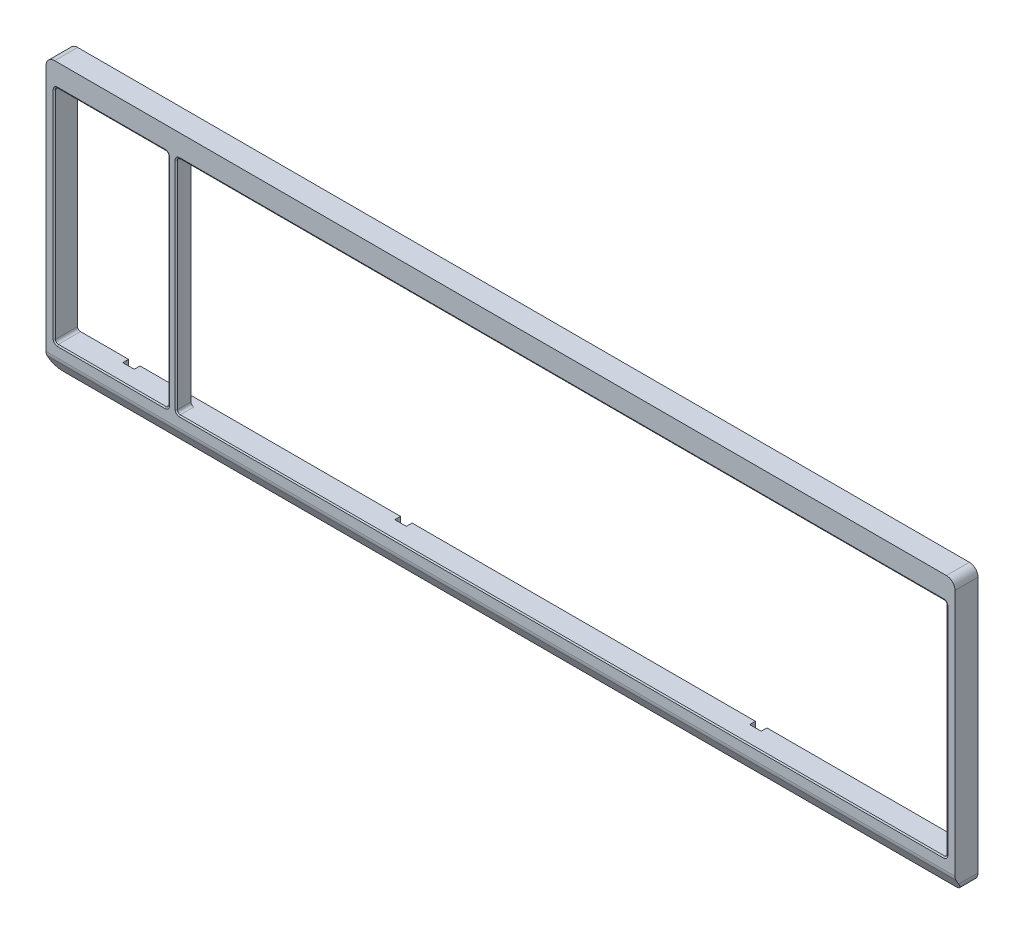
SolidWorks part; units mm, degrees
note: The reader was unsure of these and kept them because the rebuilt part matched: shared geometry of "Sketch3<3>", "Sketch8<3>", "Sketch11<3>".
ref_plane "Front Plane" through (0, 0, 0) normal (0, 0, 1) x (1, 0, 0)
ref_plane "Top Plane" through (0, 0, 0) normal (0, 1, 0) x (1, 0, 0)
ref_plane "Right Plane" through (0, 0, 0) normal (1, 0, 0) x (0, 0, -1)
sketch "Model" plane through (0, 0, 0) normal (0, 0, 1) x (1, 0, 0)
  line L0 (3.025, -2.525) -> (16.025, -2.525)
  line L1 (3.025, -16.525) -> (16.025, -16.525)
  line L2 (2.525, -3.025) -> (2.525, -16.025)
  line L3 (16.525, -3.025) -> (16.525, -16.025)
  line L4 (22.075, -2.525) -> (35.075, -2.525)
  line L5 (22.075, -16.525) -> (35.075, -16.525)
  line L6 (21.575, -3.025) -> (21.575, -16.025)
  line L7 (35.575, -3.025) -> (35.575, -16.025)
  line L8 (45.8875, -2.525) -> (58.8875, -2.525)
  line L9 (45.8875, -16.525) -> (58.8875, -16.525)
  line L10 (45.3875, -3.025) -> (45.3875, -16.025)
  line L11 (59.3875, -3.025) -> (59.3875, -16.025)
  line L12 (64.9375, -2.525) -> (77.9375, -2.525)
  line L13 (64.9375, -16.525) -> (77.9375, -16.525)
  line L14 (64.4375, -3.025) -> (64.4375, -16.025)
  line L15 (78.4375, -3.025) -> (78.4375, -16.025)
  line L16 (83.9875, -2.525) -> (96.9875, -2.525)
  line L17 (83.9875, -16.525) -> (96.9875, -16.525)
  line L18 (83.4875, -3.025) -> (83.4875, -16.025)
  line L19 (97.4875, -3.025) -> (97.4875, -16.025)
  line L20 (103.0375, -2.525) -> (116.0375, -2.525)
  line L21 (103.0375, -16.525) -> (116.0375, -16.525)
  line L22 (102.5375, -3.025) -> (102.5375, -16.025)
  line L23 (116.5375, -3.025) -> (116.5375, -16.025)
  line L24 (122.0875, -2.525) -> (135.0875, -2.525)
  line L25 (122.0875, -16.525) -> (135.0875, -16.525)
  line L26 (121.5875, -3.025) -> (121.5875, -16.025)
  line L27 (135.5875, -3.025) -> (135.5875, -16.025)
  line L28 (141.1375, -2.525) -> (154.1375, -2.525)
  line L29 (141.1375, -16.525) -> (154.1375, -16.525)
  line L30 (140.6375, -3.025) -> (140.6375, -16.025)
  line L31 (154.6375, -3.025) -> (154.6375, -16.025)
  line L32 (160.1875, -2.525) -> (173.1875, -2.525)
  line L33 (160.1875, -16.525) -> (173.1875, -16.525)
  line L34 (159.6875, -3.025) -> (159.6875, -16.025)
  line L35 (173.6875, -3.025) -> (173.6875, -16.025)
  line L36 (179.2375, -2.525) -> (192.2375, -2.525)
  line L37 (179.2375, -16.525) -> (192.2375, -16.525)
  line L38 (178.7375, -3.025) -> (178.7375, -16.025)
  line L39 (192.7375, -3.025) -> (192.7375, -16.025)
  line L40 (198.2875, -2.525) -> (211.2875, -2.525)
  line L41 (198.2875, -16.525) -> (211.2875, -16.525)
  line L42 (197.7875, -3.025) -> (197.7875, -16.025)
  line L43 (211.7875, -3.025) -> (211.7875, -16.025)
  line L44 (217.3375, -2.525) -> (230.3375, -2.525)
  line L45 (217.3375, -16.525) -> (230.3375, -16.525)
  line L46 (216.8375, -3.025) -> (216.8375, -16.025)
  line L47 (230.8375, -3.025) -> (230.8375, -16.025)
  line L48 (236.3875, -2.525) -> (249.3875, -2.525)
  line L49 (236.3875, -16.525) -> (249.3875, -16.525)
  line L50 (235.8875, -3.025) -> (235.8875, -16.025)
  line L51 (249.8875, -3.025) -> (249.8875, -16.025)
  line L52 (255.4375, -2.525) -> (268.4375, -2.525)
  line L53 (255.4375, -16.525) -> (268.4375, -16.525)
  line L54 (254.9375, -3.025) -> (254.9375, -16.025)
  line L55 (268.9375, -3.025) -> (268.9375, -16.025)
  line L56 (274.4875, -2.525) -> (287.4875, -2.525)
  line L57 (274.4875, -16.525) -> (287.4875, -16.525)
  line L58 (273.9875, -3.025) -> (273.9875, -16.025)
  line L59 (287.9875, -3.025) -> (287.9875, -16.025)
  line L60 (293.5375, -2.525) -> (306.5375, -2.525)
  line L61 (293.5375, -16.525) -> (306.5375, -16.525)
  line L62 (293.0375, -3.025) -> (293.0375, -16.025)
  line L63 (307.0375, -3.025) -> (307.0375, -16.025)
  line L64 (3.025, -21.575) -> (16.025, -21.575)
  line L65 (3.025, -35.575) -> (16.025, -35.575)
  line L66 (2.525, -22.075) -> (2.525, -35.075)
  line L67 (16.525, -22.075) -> (16.525, -35.075)
  line L68 (22.075, -21.575) -> (35.075, -21.575)
  line L69 (22.075, -35.575) -> (35.075, -35.575)
  line L70 (21.575, -22.075) -> (21.575, -35.075)
  line L71 (35.575, -22.075) -> (35.575, -35.075)
  line L72 (48.2687, -21.575) -> (61.2687, -21.575)
  line L73 (48.2687, -35.575) -> (61.2687, -35.575)
  line L74 (47.7687, -22.075) -> (47.7687, -35.075)
  line L75 (61.7687, -22.075) -> (61.7687, -35.075)
  line L76 (69.7, -21.575) -> (82.7, -21.575)
  line L77 (69.7, -35.575) -> (82.7, -35.575)
  line L78 (69.2, -22.075) -> (69.2, -35.075)
  line L79 (83.2, -22.075) -> (83.2, -35.075)
  line L80 (88.75, -21.575) -> (101.75, -21.575)
  line L81 (88.75, -35.575) -> (101.75, -35.575)
  line L82 (88.25, -22.075) -> (88.25, -35.075)
  line L83 (102.25, -22.075) -> (102.25, -35.075)
  line L84 (107.8, -21.575) -> (120.8, -21.575)
  line L85 (107.8, -35.575) -> (120.8, -35.575)
  line L86 (107.3, -22.075) -> (107.3, -35.075)
  line L87 (121.3, -22.075) -> (121.3, -35.075)
  line L88 (126.85, -21.575) -> (139.85, -21.575)
  line L89 (126.85, -35.575) -> (139.85, -35.575)
  line L90 (126.35, -22.075) -> (126.35, -35.075)
  line L91 (140.35, -22.075) -> (140.35, -35.075)
  line L92 (145.9, -21.575) -> (158.9, -21.575)
  line L93 (145.9, -35.575) -> (158.9, -35.575)
  line L94 (145.4, -22.075) -> (145.4, -35.075)
  line L95 (159.4, -22.075) -> (159.4, -35.075)
  line L96 (164.95, -21.575) -> (177.95, -21.575)
  line L97 (164.95, -35.575) -> (177.95, -35.575)
  line L98 (164.45, -22.075) -> (164.45, -35.075)
  line L99 (178.45, -22.075) -> (178.45, -35.075)
  line L100 (184, -21.575) -> (197, -21.575)
  line L101 (184, -35.575) -> (197, -35.575)
  line L102 (183.5, -22.075) -> (183.5, -35.075)
  line L103 (197.5, -22.075) -> (197.5, -35.075)
  line L104 (203.05, -21.575) -> (216.05, -21.575)
  line L105 (203.05, -35.575) -> (216.05, -35.575)
  line L106 (202.55, -22.075) -> (202.55, -35.075)
  line L107 (216.55, -22.075) -> (216.55, -35.075)
  line L108 (222.1, -21.575) -> (235.1, -21.575)
  line L109 (222.1, -35.575) -> (235.1, -35.575)
  line L110 (221.6, -22.075) -> (221.6, -35.075)
  line L111 (235.6, -22.075) -> (235.6, -35.075)
  line L112 (241.15, -21.575) -> (254.15, -21.575)
  line L113 (241.15, -35.575) -> (254.15, -35.575)
  line L114 (240.65, -22.075) -> (240.65, -35.075)
  line L115 (254.65, -22.075) -> (254.65, -35.075)
  line L116 (260.2, -21.575) -> (273.2, -21.575)
  line L117 (260.2, -35.575) -> (273.2, -35.575)
  line L118 (259.7, -22.075) -> (259.7, -35.075)
  line L119 (273.7, -22.075) -> (273.7, -35.075)
  line L120 (286.3938, -21.575) -> (299.3938, -21.575)
  line L121 (286.3938, -35.575) -> (299.3938, -35.575)
  line L122 (285.8938, -22.075) -> (285.8938, -35.075)
  line L123 (299.8938, -22.075) -> (299.8938, -35.075)
  line L124 (281.8938, -21.575) -> (282.3938, -21.575)
  line L125 (281.8938, -35.575) -> (282.3938, -35.575)
  line L126 (281.3938, -22.075) -> (281.3938, -35.075)
  line L127 (282.8938, -22.075) -> (282.8938, -35.075)
  line L128 (303.3938, -21.575) -> (303.8938, -21.575)
  line L129 (303.3938, -35.575) -> (303.8938, -35.575)
  line L130 (302.8938, -22.075) -> (302.8938, -35.075)
  line L131 (304.3938, -22.075) -> (304.3938, -35.075)
  line L132 (3.025, -40.625) -> (16.025, -40.625)
  line L133 (3.025, -54.625) -> (16.025, -54.625)
  line L134 (2.525, -41.125) -> (2.525, -54.125)
  line L135 (16.525, -41.125) -> (16.525, -54.125)
  line L136 (22.075, -40.625) -> (35.075, -40.625)
  line L137 (22.075, -54.625) -> (35.075, -54.625)
  line L138 (21.575, -41.125) -> (21.575, -54.125)
  line L139 (35.575, -41.125) -> (35.575, -54.125)
  line L140 (53.0312, -40.625) -> (66.0312, -40.625)
  line L141 (53.0312, -54.625) -> (66.0312, -54.625)
  line L142 (52.5312, -41.125) -> (52.5312, -54.125)
  line L143 (66.5312, -41.125) -> (66.5312, -54.125)
  line L144 (48.5312, -40.625) -> (49.0312, -40.625)
  line L145 (48.5312, -54.625) -> (49.0312, -54.625)
  line L146 (48.0312, -41.125) -> (48.0312, -54.125)
  line L147 (49.5312, -41.125) -> (49.5312, -54.125)
  line L148 (70.0312, -40.625) -> (70.5312, -40.625)
  line L149 (70.0312, -54.625) -> (70.5312, -54.625)
  line L150 (69.5312, -41.125) -> (69.5312, -54.125)
  line L151 (71.0312, -41.125) -> (71.0312, -54.125)
  line L152 (79.225, -40.625) -> (92.225, -40.625)
  line L153 (79.225, -54.625) -> (92.225, -54.625)
  line L154 (78.725, -41.125) -> (78.725, -54.125)
  line L155 (92.725, -41.125) -> (92.725, -54.125)
  line L156 (98.275, -40.625) -> (111.275, -40.625)
  line L157 (98.275, -54.625) -> (111.275, -54.625)
  line L158 (97.775, -41.125) -> (97.775, -54.125)
  line L159 (111.775, -41.125) -> (111.775, -54.125)
  line L160 (117.325, -40.625) -> (130.325, -40.625)
  line L161 (117.325, -54.625) -> (130.325, -54.625)
  line L162 (116.825, -41.125) -> (116.825, -54.125)
  line L163 (130.825, -41.125) -> (130.825, -54.125)
  line L164 (136.375, -40.625) -> (149.375, -40.625)
  line L165 (136.375, -54.625) -> (149.375, -54.625)
  line L166 (135.875, -41.125) -> (135.875, -54.125)
  line L167 (149.875, -41.125) -> (149.875, -54.125)
  line L168 (155.425, -40.625) -> (168.425, -40.625)
  line L169 (155.425, -54.625) -> (168.425, -54.625)
  line L170 (154.925, -41.125) -> (154.925, -54.125)
  line L171 (168.925, -41.125) -> (168.925, -54.125)
  line L172 (174.475, -40.625) -> (187.475, -40.625)
  line L173 (174.475, -54.625) -> (187.475, -54.625)
  line L174 (173.975, -41.125) -> (173.975, -54.125)
  line L175 (187.975, -41.125) -> (187.975, -54.125)
  line L176 (193.525, -40.625) -> (206.525, -40.625)
  line L177 (193.525, -54.625) -> (206.525, -54.625)
  line L178 (193.025, -41.125) -> (193.025, -54.125)
  line L179 (207.025, -41.125) -> (207.025, -54.125)
  line L180 (212.575, -40.625) -> (225.575, -40.625)
  line L181 (212.575, -54.625) -> (225.575, -54.625)
  line L182 (212.075, -41.125) -> (212.075, -54.125)
  line L183 (226.075, -41.125) -> (226.075, -54.125)
  line L184 (231.625, -40.625) -> (244.625, -40.625)
  line L185 (231.625, -54.625) -> (244.625, -54.625)
  line L186 (231.125, -41.125) -> (231.125, -54.125)
  line L187 (245.125, -41.125) -> (245.125, -54.125)
  line L188 (250.675, -40.625) -> (263.675, -40.625)
  line L189 (250.675, -54.625) -> (263.675, -54.625)
  line L190 (250.175, -41.125) -> (250.175, -54.125)
  line L191 (264.175, -41.125) -> (264.175, -54.125)
  line L192 (269.725, -40.625) -> (282.725, -40.625)
  line L193 (269.725, -54.625) -> (282.725, -54.625)
  line L194 (269.225, -41.125) -> (269.225, -54.125)
  line L195 (283.225, -41.125) -> (283.225, -54.125)
  line L196 (291.1562, -40.625) -> (304.1562, -40.625)
  line L197 (291.1562, -54.625) -> (304.1562, -54.625)
  line L198 (290.6562, -41.125) -> (290.6562, -54.125)
  line L199 (304.6562, -41.125) -> (304.6562, -54.125)
  line L200 (3.025, -59.675) -> (16.025, -59.675)
  line L201 (3.025, -73.675) -> (16.025, -73.675)
  line L202 (2.525, -60.175) -> (2.525, -73.175)
  line L203 (16.525, -60.175) -> (16.525, -73.175)
  line L204 (22.075, -59.675) -> (35.075, -59.675)
  line L205 (22.075, -73.675) -> (35.075, -73.675)
  line L206 (21.575, -60.175) -> (21.575, -73.175)
  line L207 (35.575, -60.175) -> (35.575, -73.175)
  line L208 (48.2687, -59.675) -> (61.2687, -59.675)
  line L209 (48.2687, -73.675) -> (61.2687, -73.675)
  line L210 (47.7687, -60.175) -> (47.7687, -73.175)
  line L211 (61.7687, -60.175) -> (61.7687, -73.175)
  line L212 (69.7, -59.675) -> (82.7, -59.675)
  line L213 (69.7, -73.675) -> (82.7, -73.675)
  line L214 (69.2, -60.175) -> (69.2, -73.175)
  line L215 (83.2, -60.175) -> (83.2, -73.175)
  line L216 (93.5125, -59.675) -> (106.5125, -59.675)
  line L217 (93.5125, -73.675) -> (106.5125, -73.675)
  line L218 (93.0125, -60.175) -> (93.0125, -73.175)
  line L219 (107.0125, -60.175) -> (107.0125, -73.175)
  line L220 (89.0125, -59.675) -> (89.5125, -59.675)
  line L221 (89.0125, -73.675) -> (89.5125, -73.675)
  line L222 (88.5125, -60.175) -> (88.5125, -73.175)
  line L223 (90.0125, -60.175) -> (90.0125, -73.175)
  line L224 (110.5125, -59.675) -> (111.0125, -59.675)
  line L225 (110.5125, -73.675) -> (111.0125, -73.675)
  line L226 (110.0125, -60.175) -> (110.0125, -73.175)
  line L227 (111.5125, -60.175) -> (111.5125, -73.175)
  line L228 (167.3313, -59.675) -> (180.3313, -59.675)
  line L229 (167.3313, -73.675) -> (180.3313, -73.675)
  line L230 (166.8313, -60.175) -> (166.8313, -73.175)
  line L231 (180.8313, -60.175) -> (180.8313, -73.175)
  line L232 (120.8312, -60.675) -> (126.8313, -60.675)
  line L233 (120.8312, -75.675) -> (126.8313, -75.675)
  line L234 (120.3312, -61.175) -> (120.3312, -75.175)
  line L235 (127.3313, -61.175) -> (127.3313, -75.175)
  line L236 (220.8313, -60.675) -> (226.8313, -60.675)
  line L237 (220.8313, -75.675) -> (226.8313, -75.675)
  line L238 (220.3313, -61.175) -> (220.3313, -75.175)
  line L239 (227.3313, -61.175) -> (227.3313, -75.175)
  line L240 (241.15, -59.675) -> (254.15, -59.675)
  line L241 (241.15, -73.675) -> (254.15, -73.675)
  line L242 (240.65, -60.175) -> (240.65, -73.175)
  line L243 (254.65, -60.175) -> (254.65, -73.175)
  line L244 (236.65, -59.675) -> (237.15, -59.675)
  line L245 (236.65, -73.675) -> (237.15, -73.675)
  line L246 (236.15, -60.175) -> (236.15, -73.175)
  line L247 (237.65, -60.175) -> (237.65, -73.175)
  line L248 (258.15, -59.675) -> (258.65, -59.675)
  line L249 (258.15, -73.675) -> (258.65, -73.675)
  line L250 (257.65, -60.175) -> (257.65, -73.175)
  line L251 (259.15, -60.175) -> (259.15, -73.175)
  line L252 (264.9625, -59.675) -> (277.9625, -59.675)
  line L253 (264.9625, -73.675) -> (277.9625, -73.675)
  line L254 (264.4625, -60.175) -> (264.4625, -73.175)
  line L255 (278.4625, -60.175) -> (278.4625, -73.175)
  line L256 (288.775, -59.675) -> (301.775, -59.675)
  line L257 (288.775, -73.675) -> (301.775, -73.675)
  line L258 (288.275, -60.175) -> (288.275, -73.175)
  line L259 (302.275, -60.175) -> (302.275, -73.175)
  line L260 (284.275, -59.675) -> (284.775, -59.675)
  line L261 (284.275, -73.675) -> (284.775, -73.675)
  line L262 (283.775, -60.175) -> (283.775, -73.175)
  line L263 (285.275, -60.175) -> (285.275, -73.175)
  line L264 (305.775, -59.675) -> (306.275, -59.675)
  line L265 (305.775, -73.675) -> (306.275, -73.675)
  line L266 (305.275, -60.175) -> (305.275, -73.175)
  line L267 (306.775, -60.175) -> (306.775, -73.175)
  line L268 (0, -76.2) -> (309.5625, -76.2)
  line L269 (0, 0) -> (309.5625, 0)
  line L270 (0, -76.2) -> (0, 0)
  line L271 (309.5625, -76.2) -> (309.5625, 0)
  arc A0 (3.025, -2.525) -> (2.525, -3.025) centre (3.025, -3.025) ccw
  arc A1 (16.525, -3.025) -> (16.025, -2.525) centre (16.025, -3.025) ccw
  arc A2 (2.525, -16.025) -> (3.025, -16.525) centre (3.025, -16.025) ccw
  arc A3 (16.025, -16.525) -> (16.525, -16.025) centre (16.025, -16.025) ccw
  arc A4 (22.075, -2.525) -> (21.575, -3.025) centre (22.075, -3.025) ccw
  arc A5 (35.575, -3.025) -> (35.075, -2.525) centre (35.075, -3.025) ccw
  arc A6 (21.575, -16.025) -> (22.075, -16.525) centre (22.075, -16.025) ccw
  arc A7 (35.075, -16.525) -> (35.575, -16.025) centre (35.075, -16.025) ccw
  arc A8 (45.8875, -2.525) -> (45.3875, -3.025) centre (45.8875, -3.025) ccw
  arc A9 (59.3875, -3.025) -> (58.8875, -2.525) centre (58.8875, -3.025) ccw
  arc A10 (45.3875, -16.025) -> (45.8875, -16.525) centre (45.8875, -16.025) ccw
  arc A11 (58.8875, -16.525) -> (59.3875, -16.025) centre (58.8875, -16.025) ccw
  arc A12 (64.9375, -2.525) -> (64.4375, -3.025) centre (64.9375, -3.025) ccw
  arc A13 (78.4375, -3.025) -> (77.9375, -2.525) centre (77.9375, -3.025) ccw
  arc A14 (64.4375, -16.025) -> (64.9375, -16.525) centre (64.9375, -16.025) ccw
  arc A15 (77.9375, -16.525) -> (78.4375, -16.025) centre (77.9375, -16.025) ccw
  arc A16 (83.9875, -2.525) -> (83.4875, -3.025) centre (83.9875, -3.025) ccw
  arc A17 (97.4875, -3.025) -> (96.9875, -2.525) centre (96.9875, -3.025) ccw
  arc A18 (83.4875, -16.025) -> (83.9875, -16.525) centre (83.9875, -16.025) ccw
  arc A19 (96.9875, -16.525) -> (97.4875, -16.025) centre (96.9875, -16.025) ccw
  arc A20 (103.0375, -2.525) -> (102.5375, -3.025) centre (103.0375, -3.025) ccw
  arc A21 (116.5375, -3.025) -> (116.0375, -2.525) centre (116.0375, -3.025) ccw
  arc A22 (102.5375, -16.025) -> (103.0375, -16.525) centre (103.0375, -16.025) ccw
  arc A23 (116.0375, -16.525) -> (116.5375, -16.025) centre (116.0375, -16.025) ccw
  arc A24 (122.0875, -2.525) -> (121.5875, -3.025) centre (122.0875, -3.025) ccw
  arc A25 (135.5875, -3.025) -> (135.0875, -2.525) centre (135.0875, -3.025) ccw
  arc A26 (121.5875, -16.025) -> (122.0875, -16.525) centre (122.0875, -16.025) ccw
  arc A27 (135.0875, -16.525) -> (135.5875, -16.025) centre (135.0875, -16.025) ccw
  arc A28 (141.1375, -2.525) -> (140.6375, -3.025) centre (141.1375, -3.025) ccw
  arc A29 (154.6375, -3.025) -> (154.1375, -2.525) centre (154.1375, -3.025) ccw
  arc A30 (140.6375, -16.025) -> (141.1375, -16.525) centre (141.1375, -16.025) ccw
  arc A31 (154.1375, -16.525) -> (154.6375, -16.025) centre (154.1375, -16.025) ccw
  arc A32 (160.1875, -2.525) -> (159.6875, -3.025) centre (160.1875, -3.025) ccw
  arc A33 (173.6875, -3.025) -> (173.1875, -2.525) centre (173.1875, -3.025) ccw
  arc A34 (159.6875, -16.025) -> (160.1875, -16.525) centre (160.1875, -16.025) ccw
  arc A35 (173.1875, -16.525) -> (173.6875, -16.025) centre (173.1875, -16.025) ccw
  arc A36 (179.2375, -2.525) -> (178.7375, -3.025) centre (179.2375, -3.025) ccw
  arc A37 (192.7375, -3.025) -> (192.2375, -2.525) centre (192.2375, -3.025) ccw
  arc A38 (178.7375, -16.025) -> (179.2375, -16.525) centre (179.2375, -16.025) ccw
  arc A39 (192.2375, -16.525) -> (192.7375, -16.025) centre (192.2375, -16.025) ccw
  arc A40 (198.2875, -2.525) -> (197.7875, -3.025) centre (198.2875, -3.025) ccw
  arc A41 (211.7875, -3.025) -> (211.2875, -2.525) centre (211.2875, -3.025) ccw
  arc A42 (197.7875, -16.025) -> (198.2875, -16.525) centre (198.2875, -16.025) ccw
  arc A43 (211.2875, -16.525) -> (211.7875, -16.025) centre (211.2875, -16.025) ccw
  arc A44 (217.3375, -2.525) -> (216.8375, -3.025) centre (217.3375, -3.025) ccw
  arc A45 (230.8375, -3.025) -> (230.3375, -2.525) centre (230.3375, -3.025) ccw
  arc A46 (216.8375, -16.025) -> (217.3375, -16.525) centre (217.3375, -16.025) ccw
  arc A47 (230.3375, -16.525) -> (230.8375, -16.025) centre (230.3375, -16.025) ccw
  arc A48 (236.3875, -2.525) -> (235.8875, -3.025) centre (236.3875, -3.025) ccw
  arc A49 (249.8875, -3.025) -> (249.3875, -2.525) centre (249.3875, -3.025) ccw
  arc A50 (235.8875, -16.025) -> (236.3875, -16.525) centre (236.3875, -16.025) ccw
  arc A51 (249.3875, -16.525) -> (249.8875, -16.025) centre (249.3875, -16.025) ccw
  arc A52 (255.4375, -2.525) -> (254.9375, -3.025) centre (255.4375, -3.025) ccw
  arc A53 (268.9375, -3.025) -> (268.4375, -2.525) centre (268.4375, -3.025) ccw
  arc A54 (254.9375, -16.025) -> (255.4375, -16.525) centre (255.4375, -16.025) ccw
  arc A55 (268.4375, -16.525) -> (268.9375, -16.025) centre (268.4375, -16.025) ccw
  arc A56 (274.4875, -2.525) -> (273.9875, -3.025) centre (274.4875, -3.025) ccw
  arc A57 (287.9875, -3.025) -> (287.4875, -2.525) centre (287.4875, -3.025) ccw
  arc A58 (273.9875, -16.025) -> (274.4875, -16.525) centre (274.4875, -16.025) ccw
  arc A59 (287.4875, -16.525) -> (287.9875, -16.025) centre (287.4875, -16.025) ccw
  arc A60 (293.5375, -2.525) -> (293.0375, -3.025) centre (293.5375, -3.025) ccw
  arc A61 (307.0375, -3.025) -> (306.5375, -2.525) centre (306.5375, -3.025) ccw
  arc A62 (293.0375, -16.025) -> (293.5375, -16.525) centre (293.5375, -16.025) ccw
  arc A63 (306.5375, -16.525) -> (307.0375, -16.025) centre (306.5375, -16.025) ccw
  arc A64 (3.025, -21.575) -> (2.525, -22.075) centre (3.025, -22.075) ccw
  arc A65 (16.525, -22.075) -> (16.025, -21.575) centre (16.025, -22.075) ccw
  arc A66 (2.525, -35.075) -> (3.025, -35.575) centre (3.025, -35.075) ccw
  arc A67 (16.025, -35.575) -> (16.525, -35.075) centre (16.025, -35.075) ccw
  arc A68 (22.075, -21.575) -> (21.575, -22.075) centre (22.075, -22.075) ccw
  arc A69 (35.575, -22.075) -> (35.075, -21.575) centre (35.075, -22.075) ccw
  arc A70 (21.575, -35.075) -> (22.075, -35.575) centre (22.075, -35.075) ccw
  arc A71 (35.075, -35.575) -> (35.575, -35.075) centre (35.075, -35.075) ccw
  arc A72 (48.2687, -21.575) -> (47.7687, -22.075) centre (48.2687, -22.075) ccw
  arc A73 (61.7687, -22.075) -> (61.2687, -21.575) centre (61.2687, -22.075) ccw
  arc A74 (47.7687, -35.075) -> (48.2687, -35.575) centre (48.2687, -35.075) ccw
  arc A75 (61.2687, -35.575) -> (61.7687, -35.075) centre (61.2687, -35.075) ccw
  arc A76 (69.7, -21.575) -> (69.2, -22.075) centre (69.7, -22.075) ccw
  arc A77 (83.2, -22.075) -> (82.7, -21.575) centre (82.7, -22.075) ccw
  arc A78 (69.2, -35.075) -> (69.7, -35.575) centre (69.7, -35.075) ccw
  arc A79 (82.7, -35.575) -> (83.2, -35.075) centre (82.7, -35.075) ccw
  arc A80 (88.75, -21.575) -> (88.25, -22.075) centre (88.75, -22.075) ccw
  arc A81 (102.25, -22.075) -> (101.75, -21.575) centre (101.75, -22.075) ccw
  arc A82 (88.25, -35.075) -> (88.75, -35.575) centre (88.75, -35.075) ccw
  arc A83 (101.75, -35.575) -> (102.25, -35.075) centre (101.75, -35.075) ccw
  arc A84 (107.8, -21.575) -> (107.3, -22.075) centre (107.8, -22.075) ccw
  arc A85 (121.3, -22.075) -> (120.8, -21.575) centre (120.8, -22.075) ccw
  arc A86 (107.3, -35.075) -> (107.8, -35.575) centre (107.8, -35.075) ccw
  arc A87 (120.8, -35.575) -> (121.3, -35.075) centre (120.8, -35.075) ccw
  arc A88 (126.85, -21.575) -> (126.35, -22.075) centre (126.85, -22.075) ccw
  arc A89 (140.35, -22.075) -> (139.85, -21.575) centre (139.85, -22.075) ccw
  arc A90 (126.35, -35.075) -> (126.85, -35.575) centre (126.85, -35.075) ccw
  arc A91 (139.85, -35.575) -> (140.35, -35.075) centre (139.85, -35.075) ccw
  arc A92 (145.9, -21.575) -> (145.4, -22.075) centre (145.9, -22.075) ccw
  arc A93 (159.4, -22.075) -> (158.9, -21.575) centre (158.9, -22.075) ccw
  arc A94 (145.4, -35.075) -> (145.9, -35.575) centre (145.9, -35.075) ccw
  arc A95 (158.9, -35.575) -> (159.4, -35.075) centre (158.9, -35.075) ccw
  arc A96 (164.95, -21.575) -> (164.45, -22.075) centre (164.95, -22.075) ccw
  arc A97 (178.45, -22.075) -> (177.95, -21.575) centre (177.95, -22.075) ccw
  arc A98 (164.45, -35.075) -> (164.95, -35.575) centre (164.95, -35.075) ccw
  arc A99 (177.95, -35.575) -> (178.45, -35.075) centre (177.95, -35.075) ccw
  arc A100 (184, -21.575) -> (183.5, -22.075) centre (184, -22.075) ccw
  arc A101 (197.5, -22.075) -> (197, -21.575) centre (197, -22.075) ccw
  arc A102 (183.5, -35.075) -> (184, -35.575) centre (184, -35.075) ccw
  arc A103 (197, -35.575) -> (197.5, -35.075) centre (197, -35.075) ccw
  arc A104 (203.05, -21.575) -> (202.55, -22.075) centre (203.05, -22.075) ccw
  arc A105 (216.55, -22.075) -> (216.05, -21.575) centre (216.05, -22.075) ccw
  arc A106 (202.55, -35.075) -> (203.05, -35.575) centre (203.05, -35.075) ccw
  arc A107 (216.05, -35.575) -> (216.55, -35.075) centre (216.05, -35.075) ccw
  arc A108 (222.1, -21.575) -> (221.6, -22.075) centre (222.1, -22.075) ccw
  arc A109 (235.6, -22.075) -> (235.1, -21.575) centre (235.1, -22.075) ccw
  arc A110 (221.6, -35.075) -> (222.1, -35.575) centre (222.1, -35.075) ccw
  arc A111 (235.1, -35.575) -> (235.6, -35.075) centre (235.1, -35.075) ccw
  arc A112 (241.15, -21.575) -> (240.65, -22.075) centre (241.15, -22.075) ccw
  arc A113 (254.65, -22.075) -> (254.15, -21.575) centre (254.15, -22.075) ccw
  arc A114 (240.65, -35.075) -> (241.15, -35.575) centre (241.15, -35.075) ccw
  arc A115 (254.15, -35.575) -> (254.65, -35.075) centre (254.15, -35.075) ccw
  arc A116 (260.2, -21.575) -> (259.7, -22.075) centre (260.2, -22.075) ccw
  arc A117 (273.7, -22.075) -> (273.2, -21.575) centre (273.2, -22.075) ccw
  arc A118 (259.7, -35.075) -> (260.2, -35.575) centre (260.2, -35.075) ccw
  arc A119 (273.2, -35.575) -> (273.7, -35.075) centre (273.2, -35.075) ccw
  arc A120 (286.3938, -21.575) -> (285.8938, -22.075) centre (286.3938, -22.075) ccw
  arc A121 (299.8938, -22.075) -> (299.3938, -21.575) centre (299.3938, -22.075) ccw
  arc A122 (285.8938, -35.075) -> (286.3938, -35.575) centre (286.3938, -35.075) ccw
  arc A123 (299.3938, -35.575) -> (299.8938, -35.075) centre (299.3938, -35.075) ccw
  arc A124 (281.8938, -21.575) -> (281.3938, -22.075) centre (281.8938, -22.075) ccw
  arc A125 (282.8938, -22.075) -> (282.3938, -21.575) centre (282.3938, -22.075) ccw
  arc A126 (281.3938, -35.075) -> (281.8938, -35.575) centre (281.8938, -35.075) ccw
  arc A127 (282.3938, -35.575) -> (282.8938, -35.075) centre (282.3938, -35.075) ccw
  arc A128 (303.3938, -21.575) -> (302.8938, -22.075) centre (303.3938, -22.075) ccw
  arc A129 (304.3938, -22.075) -> (303.8938, -21.575) centre (303.8938, -22.075) ccw
  arc A130 (302.8938, -35.075) -> (303.3938, -35.575) centre (303.3938, -35.075) ccw
  arc A131 (303.8938, -35.575) -> (304.3938, -35.075) centre (303.8938, -35.075) ccw
  arc A132 (3.025, -40.625) -> (2.525, -41.125) centre (3.025, -41.125) ccw
  arc A133 (16.525, -41.125) -> (16.025, -40.625) centre (16.025, -41.125) ccw
  arc A134 (2.525, -54.125) -> (3.025, -54.625) centre (3.025, -54.125) ccw
  arc A135 (16.025, -54.625) -> (16.525, -54.125) centre (16.025, -54.125) ccw
  arc A136 (22.075, -40.625) -> (21.575, -41.125) centre (22.075, -41.125) ccw
  arc A137 (35.575, -41.125) -> (35.075, -40.625) centre (35.075, -41.125) ccw
  arc A138 (21.575, -54.125) -> (22.075, -54.625) centre (22.075, -54.125) ccw
  arc A139 (35.075, -54.625) -> (35.575, -54.125) centre (35.075, -54.125) ccw
  arc A140 (53.0312, -40.625) -> (52.5312, -41.125) centre (53.0312, -41.125) ccw
  arc A141 (66.5312, -41.125) -> (66.0312, -40.625) centre (66.0312, -41.125) ccw
  arc A142 (52.5312, -54.125) -> (53.0312, -54.625) centre (53.0312, -54.125) ccw
  arc A143 (66.0312, -54.625) -> (66.5312, -54.125) centre (66.0312, -54.125) ccw
  arc A144 (48.5312, -40.625) -> (48.0312, -41.125) centre (48.5312, -41.125) ccw
  arc A145 (49.5312, -41.125) -> (49.0312, -40.625) centre (49.0312, -41.125) ccw
  arc A146 (48.0312, -54.125) -> (48.5312, -54.625) centre (48.5312, -54.125) ccw
  arc A147 (49.0312, -54.625) -> (49.5312, -54.125) centre (49.0312, -54.125) ccw
  arc A148 (70.0312, -40.625) -> (69.5312, -41.125) centre (70.0312, -41.125) ccw
  arc A149 (71.0312, -41.125) -> (70.5312, -40.625) centre (70.5312, -41.125) ccw
  arc A150 (69.5312, -54.125) -> (70.0312, -54.625) centre (70.0312, -54.125) ccw
  arc A151 (70.5312, -54.625) -> (71.0312, -54.125) centre (70.5312, -54.125) ccw
  arc A152 (79.225, -40.625) -> (78.725, -41.125) centre (79.225, -41.125) ccw
  arc A153 (92.725, -41.125) -> (92.225, -40.625) centre (92.225, -41.125) ccw
  arc A154 (78.725, -54.125) -> (79.225, -54.625) centre (79.225, -54.125) ccw
  arc A155 (92.225, -54.625) -> (92.725, -54.125) centre (92.225, -54.125) ccw
  arc A156 (98.275, -40.625) -> (97.775, -41.125) centre (98.275, -41.125) ccw
  arc A157 (111.775, -41.125) -> (111.275, -40.625) centre (111.275, -41.125) ccw
  arc A158 (97.775, -54.125) -> (98.275, -54.625) centre (98.275, -54.125) ccw
  arc A159 (111.275, -54.625) -> (111.775, -54.125) centre (111.275, -54.125) ccw
  arc A160 (117.325, -40.625) -> (116.825, -41.125) centre (117.325, -41.125) ccw
  arc A161 (130.825, -41.125) -> (130.325, -40.625) centre (130.325, -41.125) ccw
  arc A162 (116.825, -54.125) -> (117.325, -54.625) centre (117.325, -54.125) ccw
  arc A163 (130.325, -54.625) -> (130.825, -54.125) centre (130.325, -54.125) ccw
  arc A164 (136.375, -40.625) -> (135.875, -41.125) centre (136.375, -41.125) ccw
  arc A165 (149.875, -41.125) -> (149.375, -40.625) centre (149.375, -41.125) ccw
  arc A166 (135.875, -54.125) -> (136.375, -54.625) centre (136.375, -54.125) ccw
  arc A167 (149.375, -54.625) -> (149.875, -54.125) centre (149.375, -54.125) ccw
  arc A168 (155.425, -40.625) -> (154.925, -41.125) centre (155.425, -41.125) ccw
  arc A169 (168.925, -41.125) -> (168.425, -40.625) centre (168.425, -41.125) ccw
  arc A170 (154.925, -54.125) -> (155.425, -54.625) centre (155.425, -54.125) ccw
  arc A171 (168.425, -54.625) -> (168.925, -54.125) centre (168.425, -54.125) ccw
  arc A172 (174.475, -40.625) -> (173.975, -41.125) centre (174.475, -41.125) ccw
  arc A173 (187.975, -41.125) -> (187.475, -40.625) centre (187.475, -41.125) ccw
  arc A174 (173.975, -54.125) -> (174.475, -54.625) centre (174.475, -54.125) ccw
  arc A175 (187.475, -54.625) -> (187.975, -54.125) centre (187.475, -54.125) ccw
  arc A176 (193.525, -40.625) -> (193.025, -41.125) centre (193.525, -41.125) ccw
  arc A177 (207.025, -41.125) -> (206.525, -40.625) centre (206.525, -41.125) ccw
  arc A178 (193.025, -54.125) -> (193.525, -54.625) centre (193.525, -54.125) ccw
  arc A179 (206.525, -54.625) -> (207.025, -54.125) centre (206.525, -54.125) ccw
  arc A180 (212.575, -40.625) -> (212.075, -41.125) centre (212.575, -41.125) ccw
  arc A181 (226.075, -41.125) -> (225.575, -40.625) centre (225.575, -41.125) ccw
  arc A182 (212.075, -54.125) -> (212.575, -54.625) centre (212.575, -54.125) ccw
  arc A183 (225.575, -54.625) -> (226.075, -54.125) centre (225.575, -54.125) ccw
  arc A184 (231.625, -40.625) -> (231.125, -41.125) centre (231.625, -41.125) ccw
  arc A185 (245.125, -41.125) -> (244.625, -40.625) centre (244.625, -41.125) ccw
  arc A186 (231.125, -54.125) -> (231.625, -54.625) centre (231.625, -54.125) ccw
  arc A187 (244.625, -54.625) -> (245.125, -54.125) centre (244.625, -54.125) ccw
  arc A188 (250.675, -40.625) -> (250.175, -41.125) centre (250.675, -41.125) ccw
  arc A189 (264.175, -41.125) -> (263.675, -40.625) centre (263.675, -41.125) ccw
  arc A190 (250.175, -54.125) -> (250.675, -54.625) centre (250.675, -54.125) ccw
  arc A191 (263.675, -54.625) -> (264.175, -54.125) centre (263.675, -54.125) ccw
  arc A192 (269.725, -40.625) -> (269.225, -41.125) centre (269.725, -41.125) ccw
  arc A193 (283.225, -41.125) -> (282.725, -40.625) centre (282.725, -41.125) ccw
  arc A194 (269.225, -54.125) -> (269.725, -54.625) centre (269.725, -54.125) ccw
  arc A195 (282.725, -54.625) -> (283.225, -54.125) centre (282.725, -54.125) ccw
  arc A196 (291.1562, -40.625) -> (290.6562, -41.125) centre (291.1562, -41.125) ccw
  arc A197 (304.6562, -41.125) -> (304.1562, -40.625) centre (304.1562, -41.125) ccw
  arc A198 (290.6562, -54.125) -> (291.1562, -54.625) centre (291.1562, -54.125) ccw
  arc A199 (304.1562, -54.625) -> (304.6562, -54.125) centre (304.1562, -54.125) ccw
  arc A200 (3.025, -59.675) -> (2.525, -60.175) centre (3.025, -60.175) ccw
  arc A201 (16.525, -60.175) -> (16.025, -59.675) centre (16.025, -60.175) ccw
  arc A202 (2.525, -73.175) -> (3.025, -73.675) centre (3.025, -73.175) ccw
  arc A203 (16.025, -73.675) -> (16.525, -73.175) centre (16.025, -73.175) ccw
  arc A204 (22.075, -59.675) -> (21.575, -60.175) centre (22.075, -60.175) ccw
  arc A205 (35.575, -60.175) -> (35.075, -59.675) centre (35.075, -60.175) ccw
  arc A206 (21.575, -73.175) -> (22.075, -73.675) centre (22.075, -73.175) ccw
  arc A207 (35.075, -73.675) -> (35.575, -73.175) centre (35.075, -73.175) ccw
  arc A208 (48.2687, -59.675) -> (47.7687, -60.175) centre (48.2687, -60.175) ccw
  arc A209 (61.7687, -60.175) -> (61.2687, -59.675) centre (61.2687, -60.175) ccw
  arc A210 (47.7687, -73.175) -> (48.2687, -73.675) centre (48.2687, -73.175) ccw
  arc A211 (61.2687, -73.675) -> (61.7687, -73.175) centre (61.2687, -73.175) ccw
  arc A212 (69.7, -59.675) -> (69.2, -60.175) centre (69.7, -60.175) ccw
  arc A213 (83.2, -60.175) -> (82.7, -59.675) centre (82.7, -60.175) ccw
  arc A214 (69.2, -73.175) -> (69.7, -73.675) centre (69.7, -73.175) ccw
  arc A215 (82.7, -73.675) -> (83.2, -73.175) centre (82.7, -73.175) ccw
  arc A216 (93.5125, -59.675) -> (93.0125, -60.175) centre (93.5125, -60.175) ccw
  arc A217 (107.0125, -60.175) -> (106.5125, -59.675) centre (106.5125, -60.175) ccw
  arc A218 (93.0125, -73.175) -> (93.5125, -73.675) centre (93.5125, -73.175) ccw
  arc A219 (106.5125, -73.675) -> (107.0125, -73.175) centre (106.5125, -73.175) ccw
  arc A220 (89.0125, -59.675) -> (88.5125, -60.175) centre (89.0125, -60.175) ccw
  arc A221 (90.0125, -60.175) -> (89.5125, -59.675) centre (89.5125, -60.175) ccw
  arc A222 (88.5125, -73.175) -> (89.0125, -73.675) centre (89.0125, -73.175) ccw
  arc A223 (89.5125, -73.675) -> (90.0125, -73.175) centre (89.5125, -73.175) ccw
  arc A224 (110.5125, -59.675) -> (110.0125, -60.175) centre (110.5125, -60.175) ccw
  arc A225 (111.5125, -60.175) -> (111.0125, -59.675) centre (111.0125, -60.175) ccw
  arc A226 (110.0125, -73.175) -> (110.5125, -73.675) centre (110.5125, -73.175) ccw
  arc A227 (111.0125, -73.675) -> (111.5125, -73.175) centre (111.0125, -73.175) ccw
  arc A228 (167.3313, -59.675) -> (166.8313, -60.175) centre (167.3313, -60.175) ccw
  arc A229 (180.8313, -60.175) -> (180.3313, -59.675) centre (180.3313, -60.175) ccw
  arc A230 (166.8313, -73.175) -> (167.3313, -73.675) centre (167.3313, -73.175) ccw
  arc A231 (180.3313, -73.675) -> (180.8313, -73.175) centre (180.3313, -73.175) ccw
  arc A232 (120.8312, -60.675) -> (120.3312, -61.175) centre (120.8312, -61.175) ccw
  arc A233 (127.3313, -61.175) -> (126.8313, -60.675) centre (126.8313, -61.175) ccw
  arc A234 (120.3312, -75.175) -> (120.8312, -75.675) centre (120.8312, -75.175) ccw
  arc A235 (126.8313, -75.675) -> (127.3313, -75.175) centre (126.8313, -75.175) ccw
  arc A236 (220.8313, -60.675) -> (220.3313, -61.175) centre (220.8313, -61.175) ccw
  arc A237 (227.3313, -61.175) -> (226.8313, -60.675) centre (226.8313, -61.175) ccw
  arc A238 (220.3313, -75.175) -> (220.8313, -75.675) centre (220.8313, -75.175) ccw
  arc A239 (226.8313, -75.675) -> (227.3313, -75.175) centre (226.8313, -75.175) ccw
  arc A240 (241.15, -59.675) -> (240.65, -60.175) centre (241.15, -60.175) ccw
  arc A241 (254.65, -60.175) -> (254.15, -59.675) centre (254.15, -60.175) ccw
  arc A242 (240.65, -73.175) -> (241.15, -73.675) centre (241.15, -73.175) ccw
  arc A243 (254.15, -73.675) -> (254.65, -73.175) centre (254.15, -73.175) ccw
  arc A244 (236.65, -59.675) -> (236.15, -60.175) centre (236.65, -60.175) ccw
  arc A245 (237.65, -60.175) -> (237.15, -59.675) centre (237.15, -60.175) ccw
  arc A246 (236.15, -73.175) -> (236.65, -73.675) centre (236.65, -73.175) ccw
  arc A247 (237.15, -73.675) -> (237.65, -73.175) centre (237.15, -73.175) ccw
  arc A248 (258.15, -59.675) -> (257.65, -60.175) centre (258.15, -60.175) ccw
  arc A249 (259.15, -60.175) -> (258.65, -59.675) centre (258.65, -60.175) ccw
  arc A250 (257.65, -73.175) -> (258.15, -73.675) centre (258.15, -73.175) ccw
  arc A251 (258.65, -73.675) -> (259.15, -73.175) centre (258.65, -73.175) ccw
  arc A252 (264.9625, -59.675) -> (264.4625, -60.175) centre (264.9625, -60.175) ccw
  arc A253 (278.4625, -60.175) -> (277.9625, -59.675) centre (277.9625, -60.175) ccw
  arc A254 (264.4625, -73.175) -> (264.9625, -73.675) centre (264.9625, -73.175) ccw
  arc A255 (277.9625, -73.675) -> (278.4625, -73.175) centre (277.9625, -73.175) ccw
  arc A256 (288.775, -59.675) -> (288.275, -60.175) centre (288.775, -60.175) ccw
  arc A257 (302.275, -60.175) -> (301.775, -59.675) centre (301.775, -60.175) ccw
  arc A258 (288.275, -73.175) -> (288.775, -73.675) centre (288.775, -73.175) ccw
  arc A259 (301.775, -73.675) -> (302.275, -73.175) centre (301.775, -73.175) ccw
  arc A260 (284.275, -59.675) -> (283.775, -60.175) centre (284.275, -60.175) ccw
  arc A261 (285.275, -60.175) -> (284.775, -59.675) centre (284.775, -60.175) ccw
  arc A262 (283.775, -73.175) -> (284.275, -73.675) centre (284.275, -73.175) ccw
  arc A263 (284.775, -73.675) -> (285.275, -73.175) centre (284.775, -73.175) ccw
  arc A264 (305.775, -59.675) -> (305.275, -60.175) centre (305.775, -60.175) ccw
  arc A265 (306.775, -60.175) -> (306.275, -59.675) centre (306.275, -60.175) ccw
  arc A266 (305.275, -73.175) -> (305.775, -73.675) centre (305.775, -73.175) ccw
  arc A267 (306.275, -73.675) -> (306.775, -73.175) centre (306.275, -73.175) ccw
sketch "Sketch3" plane through (0, 0, 0) normal (0, 0, 1) x (1, 0, 0)
  line L8 (38.9813, 0.5) -> (38.9812, -76.7)
  line L9 (-3.5, 8.5) -> (313.0625, 8.5)
  line L10 (-3.5, 8.5) -> (-3.5, -86.7)
  line L11 (-3.5, -86.7) -> (313.0625, -86.7)
  line L12 (310.0625, 0.5) -> (-0.5, 0.5)
  line L13 (310.0625, -76.7) -> (310.0625, 0.5)
  line L14 (-0.5, -76.7) -> (310.0625, -76.7)
  line L15 (-0.5, 0.5) -> (-0.5, -76.7)
  line L16 (310.0625, 0.5) -> (41.9813, 0.5)
  line L17 (310.0625, -76.7) -> (310.0625, 0.5)
  line L18 (-0.5, -76.7) -> (38.9812, -76.7)
  line L19 (-0.5, 0.5) -> (-0.5, -76.7)
  line L20 (313.0625, 8.5) -> (313.0625, -86.7)
  line L21 (41.9813, 0.5) -> (41.9813, -76.7)
  line L22 (38.9813, 0.5) -> (-0.5, 0.5)
  line L23 (41.9813, -76.7) -> (310.0625, -76.7)
  line L24 (38.9813, 0.5) -> (41.9813, 0.5)
  line L25 (35.575, -3.025) -> (35.575, -16.025) construction
  line L26 (45.3875, -3.025) -> (45.3875, -16.025) construction
  line L27 (35.575, -9.525) -> (45.3875, -9.525) construction
  line L28 (0, 0) -> (309.5625, 0) construction
  line L29 (38.9812, -76.7) -> (41.9813, -76.7)
  point P5 (40.4813, 0.5)
  point P20 (40.4813, -9.525)
  point P22 (154.7812, 0)
  point P23 (154.7812, 8.5)
  dimension "D2" = 3
  dimension "D3" = 8
  dimension "D4" = 10
  dimension "D5" = 3
  dimension "D1" = 0.5
extrude "Boss-Extrude1" add sketch "Sketch3" against normal blind 8 contours L20 L9 L10 L11 L29 L18 L19 L22 L24 L16 L17 L23
extrude "Boss-Extrude2" add sketch "Sketch3<3>" against normal blind 5 contours L27 L8 L29 L21 | L8 L27 L21 L24
sketch "Sketch3<3>" plane through (0, 0, 0) normal (0, 0, 1) x (1, 0, 0) same geometry as "Sketch3"
chamfer "Chamfer1" distance 3 angle 60 1 edges at (154.7812, -86.7, 0)
fillet "Fillet3" radius 3 1 edges at (154.7812, -81.5038, 0)
sketch "Sketch8" plane through (0, 0, -8) normal (0, 0, -1) x (-1, 0, 0)
  line L0 (-260.0625, 0.5) -> (-260.0625, 4)
  line L1 (-310.0625, 0.5) -> (0.5, 0.5) construction
  line L2 (-258.5625, 5.5) -> (-257.5625, 5.5)
  line L3 (-256.0625, 4) -> (-256.0625, 0.5)
  line L4 (-256.0625, 0.5) -> (-260.0625, 0.5)
  line L5 (-115.9813, -76.7) -> (-115.9813, -80.2)
  line L6 (-210.0625, 0.5) -> (-210.0625, 4)
  line L7 (-208.5625, 5.5) -> (-207.5625, 5.5)
  line L8 (-206.0625, 4) -> (-206.0625, 0.5)
  line L9 (-206.0625, 0.5) -> (-210.0625, 0.5)
  line L10 (-310.0625, 0.5) -> (0.5, 0.5) construction
  line L11 (-130.9813, 0.5) -> (-130.9812, 4)
  line L12 (-129.4813, 5.5) -> (-128.4813, 5.5)
  line L13 (-126.9813, 4) -> (-126.9813, 0.5)
  line L14 (-126.9813, 0.5) -> (-130.9813, 0.5)
  line L15 (-85.9813, 0.5) -> (-85.9813, 4)
  line L16 (-84.4813, 5.5) -> (-83.4813, 5.5)
  line L17 (-81.9813, 4) -> (-81.9813, 0.5)
  line L18 (-81.9813, 0.5) -> (-85.9813, 0.5)
  line L19 (-41.9813, 0.5) -> (-41.9813, -76.7) construction
  line L20 (-310.0625, -76.7) -> (-310.0625, 0.5) construction
  line L21 (-21.2406, 0.5) -> (-21.2406, 4)
  line L22 (-19.7406, 5.5) -> (-18.7406, 5.5)
  line L23 (-17.2406, 4) -> (-17.2406, 0.5)
  line L24 (-17.2406, 0.5) -> (-21.2406, 0.5)
  line L25 (-38.9813, 0.5) -> (0.5, 0.5) construction
  line L26 (-239.5625, -76.7) -> (-239.5625, -80.2)
  line L27 (0.5, -76.7) -> (-310.0625, -76.7) construction
  line L28 (-238.0625, -81.7) -> (-237.0625, -81.7)
  line L29 (-235.5625, -80.2) -> (-235.5625, -76.7)
  line L30 (-235.5625, -76.7) -> (-239.5625, -76.7)
  line L31 (-309.5625, -76.2) -> (-309.5625, 0) construction
  line L32 (-114.4813, -81.7) -> (-113.4813, -81.7)
  line L33 (-111.9813, -80.2) -> (-111.9813, -76.7)
  line L34 (-111.9813, -76.7) -> (-115.9813, -76.7)
  line L35 (-21.2406, -76.7) -> (-21.2406, -80.2)
  line L36 (-19.7406, -81.7) -> (-18.7406, -81.7)
  line L37 (-17.2406, -80.2) -> (-17.2406, -76.7)
  line L38 (-17.2406, -76.7) -> (-21.2406, -76.7)
  line L39 (-128.9813, 5.5) -> (-128.9813, 2.8) construction
  line L40 (0.5, -76.7) -> (-38.9812, -76.7) construction
  line L41 (-128.9813, 2.8) -> (-128.9813, 0.5) construction
  line L42 (-258.0625, 0.5) -> (-258.0625, 2.8) construction
  line L43 (-258.0625, 2.8) -> (-258.0625, 5.5) construction
  line L44 (-208.0625, 0.5) -> (-208.0625, 2.8) construction
  line L45 (-208.0625, 2.8) -> (-208.0625, 5.5) construction
  line L46 (-83.9813, 0.5) -> (-83.9813, 2.8) construction
  line L47 (-83.9813, 2.8) -> (-83.9813, 5.5) construction
  line L48 (-19.2406, 0.5) -> (-19.2406, 2.8) construction
  line L49 (-19.2406, 2.8) -> (-19.2406, 5.5) construction
  line L50 (-19.2406, -76.7) -> (-19.2406, -79) construction
  line L51 (-19.2406, -79) -> (-19.2406, -81.7) construction
  line L52 (-237.5625, -76.7) -> (-237.5625, -79) construction
  line L53 (-237.5625, -79) -> (-237.5625, -81.7) construction
  line L54 (-113.9813, -76.7) -> (-113.9813, -79) construction
  line L55 (-113.9813, -79) -> (-113.9813, -81.7) construction
  arc A0 (-260.0625, 4) -> (-258.5625, 5.5) centre (-258.5625, 4) cw
  arc A1 (-257.5625, 5.5) -> (-256.0625, 4) centre (-257.5625, 4) cw
  arc A2 (-210.0625, 4) -> (-208.5625, 5.5) centre (-208.5625, 4) cw
  arc A3 (-207.5625, 5.5) -> (-206.0625, 4) centre (-207.5625, 4) cw
  arc A4 (-130.9812, 4) -> (-129.4813, 5.5) centre (-129.4813, 4) cw
  arc A5 (-128.4813, 5.5) -> (-126.9813, 4) centre (-128.4813, 4) cw
  arc A6 (-85.9813, 4) -> (-84.4813, 5.5) centre (-84.4813, 4) cw
  arc A7 (-83.4813, 5.5) -> (-81.9813, 4) centre (-83.4813, 4) cw
  arc A8 (-21.2406, 4) -> (-19.7406, 5.5) centre (-19.7406, 4) cw
  arc A9 (-18.7406, 5.5) -> (-17.2406, 4) centre (-18.7406, 4) cw
  arc A10 (-239.5625, -80.2) -> (-238.0625, -81.7) centre (-238.0625, -80.2) ccw
  arc A11 (-237.0625, -81.7) -> (-235.5625, -80.2) centre (-237.0625, -80.2) ccw
  arc A12 (-115.9813, -80.2) -> (-114.4813, -81.7) centre (-114.4813, -80.2) ccw
  arc A13 (-113.4813, -81.7) -> (-111.9813, -80.2) centre (-113.4813, -80.2) ccw
  arc A14 (-21.2406, -80.2) -> (-19.7406, -81.7) centre (-19.7406, -80.2) ccw
  arc A15 (-18.7406, -81.7) -> (-17.2406, -80.2) centre (-18.7406, -80.2) ccw
  circle A16 centre (-258.0625, 2.8) radius 1.45
  circle A17 centre (-208.0625, 2.8) radius 1.45
  circle A18 centre (-128.9813, 2.8) radius 1.45
  circle A19 centre (-83.9813, 2.8) radius 1.45
  circle A20 centre (-19.2406, 2.8) radius 1.45
  circle A21 centre (-19.2406, -79) radius 1.45
  circle A22 centre (-113.9813, -79) radius 1.45
  circle A23 centre (-237.5625, -79) radius 1.45
  point P62 (-19.2406, 0.5)
  point P63 (-19.2406, 0.5)
  point P88 (-19.2406, -76.7)
  point P89 (-19.2406, -76.7)
  point P102 (-258.0625, 5.5)
  point P104 (-208.0625, 5.5)
  point P106 (-128.9813, 5.5)
  dimension "D1" = 1.5
  dimension "D5" = 2.9
  dimension "D3" = 4
  dimension "D4" = 50
  dimension "D6" = 5
  dimension "D7" = 2.3
  dimension "D14" = 40
  dimension "D15" = 85
  dimension "D16" = 100
  dimension "D23" = 70
  dimension "D27" = 70
extrude "Cut-Extrude1" cut sketch "Sketch8" against normal blind 2
extrude "Cut-Extrude4" cut sketch "Sketch8<3>" against normal offset from surface (6 mm away) 4 contours A16 | A17 | A18 | A19 | A20 | A21 | A22 | A23 up to face at (236.1125, -79, -6)
sketch "Sketch8<3>" plane through (0, 0, -8) normal (0, 0, -1) x (-1, 0, 0) same geometry as "Sketch8"
fillet "Fillet1" radius 3 4 edges at (-3.5, -86.7, -5.5) (313.0625, -86.7, -5.5) (313.0625, 8.5, -4) (-3.5, 8.5, -4)
fillet "Fillet5" radius 1 8 edges at (310.0625, -76.7, -4) (310.0625, 0.5, -4) (41.9813, 0.5, -2.5) (41.9813, -76.7, -2.5) (38.9812, -76.7, -2.5) (-0.5, -76.7, -4) (-0.5, 0.5, -4) (38.9812, 0.5, -2.5)
chamfer "Chamfer2" distance 0.5 angle 30 16 edges at (310.0625, -38.1, 0) (41.9813, -38.1, 0) (38.9812, -38.1, 0) (-0.5, -38.1, 0) (19.2406, -76.7, 0) (176.0219, -76.7, 0) (309.7696, -76.4071, 0) (309.7696, 0.2071, 0) (42.2741, -76.4071, 0) (176.0219, 0.5, 0) (42.2741, 0.2071, 0) (38.6884, -76.4071, 0) (-0.2071, -76.4071, 0) (38.6884, 0.2071, 0) (19.2406, 0.5, 0) (-0.2071, 0.2071, 0)
fillet "Fillet6" radius 0.5 2 edges at (256.0625, 0.5, -7) (260.0625, 0.5, -7)
hole_wizard "CBORE for M2 SHCS2" positions "Sketch6" profile "Sketch7" counterbore size "M2" standard "ANSI Metric"
sketch "Sketch6" plane through (0, -0.7207, -17.0827) normal (0, 0, -1) x (-1, 0, 0)
  line L2 (-304.7812, 3.7435) -> (-4.7812, 3.7435) construction
  point P0 (-304.7812, 3.7435)
  point P6 (-4.7812, 3.7435)
  point P50 (-154.7812, 3.7435)
  point P69 (-289.7812, 3.7435)
  point P71 (-12.7812, 3.7435)
  dimension "D1" = 300
  dimension "D3" = 8
  dimension "D4" = 15
sketch "Sketch7" plane through (304.7813, 3.0228, -17.0827) normal (1, 0, 0) x (0, 1, 0)
  line L0 (0, 0) -> (0, 15)
  line L1 (0, 15) -> (1.2, 14.279)
  line L2 (1.2, 14.279) -> (1.2, 4)
  line L3 (1.2, 4) -> (2.2, 4)
  line L4 (2.2, 4) -> (2.2, 0)
  line L5 (2.2, 0) -> (0, 0)
  line L6 (0, 15) -> (-1.2, 14.279) construction
  line L7 (0, -6.35) -> (0, 107.95) construction
  dimension "Hole Dia." = 2.4
  dimension "Hole Depth" = 15
  dimension "C'Bore Dia." = 4.4
  dimension "C'Bore Depth" = 4
  dimension "Drill Angle" = 118
hole_wizard "" positions "Sketch9" profile "Sketch10" countersink size "M2" standard "ANSI Metric"
sketch "Sketch9" plane through (0, 0, -9.7996) normal (0, 0, 1) x (1, 0, 0)
  line L0 (304.7812, -80.8742) -> (4.7813, -80.8742) construction
  point P0 (4.7813, -80.8742)
  point P2 (304.7812, -80.8742)
  point P9 (154.7812, -80.8742)
  point P12 (289.7812, -80.8742)
  point P14 (12.7813, -80.8742)
  dimension "D2" = 300
  dimension "D3" = 15
  dimension "D4" = 8
sketch "Sketch10" plane through (4.7813, -80.8742, -9.7996) normal (1, 0, 0) x (0, 1, 0)
  line L0 (0, 0) -> (0, 9)
  line L1 (0, 9) -> (1.2, 8.279)
  line L2 (1.2, 8.279) -> (1.2, 1)
  line L3 (1.2, 1) -> (2.2, 0)
  line L4 (2.2, 0) -> (0, 0)
  line L5 (-1.2, 1) -> (-2.2, 0) construction
  line L6 (0, 9) -> (-1.2, 8.279) construction
  line L7 (0, -6.35) -> (0, 107.95) construction
  dimension "Hole Dia." = 2.4
  dimension "Hole Depth" = 9
  dimension "Near C'Sink Dia." = 4.4
  dimension "Near C'Sink Angle" = 90
  dimension "Drill Angle" = 118
sketch "Sketch11" plane through (0, 0, -8) normal (0, 0, -1) x (-1, 0, 0)
  circle A0 centre (-304.7813, 3.0228) radius 1.45
  circle A1 centre (-289.7813, 3.0228) radius 1.45
  circle A2 centre (-12.7812, 3.0228) radius 1.45
  circle A3 centre (-4.7812, 3.0228) radius 1.45
  circle A4 centre (-4.7813, -80.8742) radius 1.45
  circle A5 centre (-12.7813, -80.8742) radius 1.45
  circle A6 centre (-289.7812, -80.8742) radius 1.45
  circle A7 centre (-304.7812, -80.8742) radius 1.45
  point P24 (0, 0)
  dimension "D1" = 2.9
extrude "Cut-Extrude2" cut sketch "Sketch11" against normal blind 4 contours A0 | A1 | A2 | A3
extrude "Cut-Extrude3" cut sketch "Sketch11<3>" against normal blind 4
sketch "Sketch11<3>" plane through (0, 0, -8) normal (0, 0, -1) x (-1, 0, 0) same geometry as "Sketch11"
